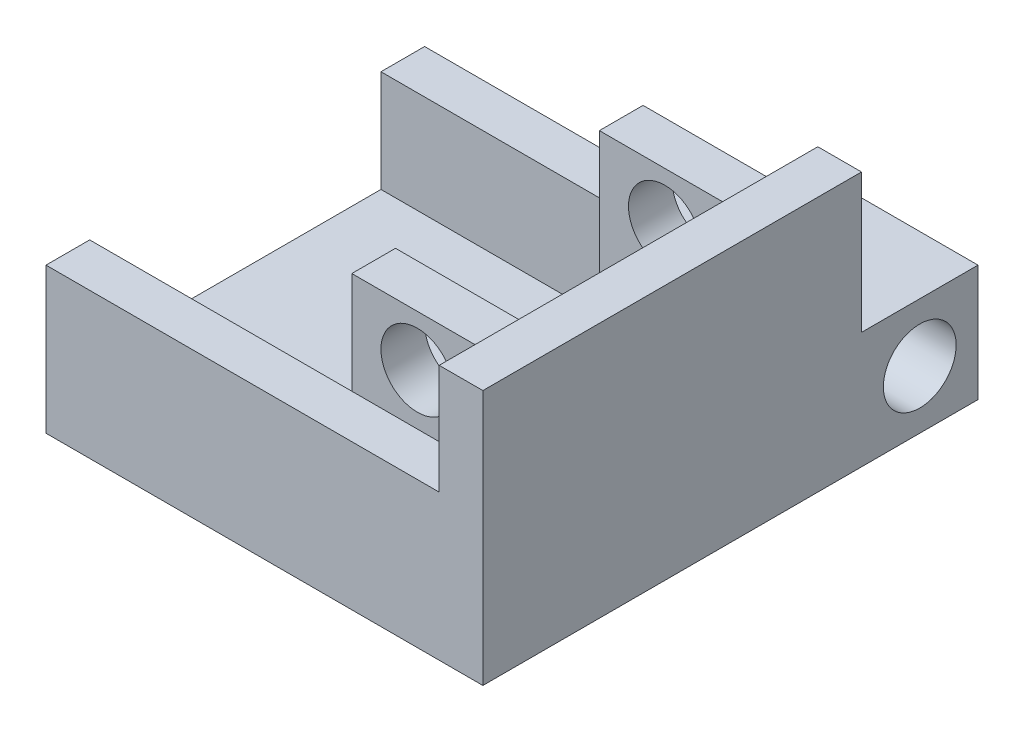
SolidWorks part; units mm, degrees
ref_plane "Front Plane" through (0, 0, 0) normal (0, 0, 1) x (1, 0, 0)
ref_plane "Top Plane" through (0, 0, 0) normal (0, 1, 0) x (1, 0, 0)
ref_plane "Right Plane" through (0, 0, 0) normal (1, 0, 0) x (0, 0, -1)
sketch "Sketch1" plane through (0, 0, 0) normal (0, 1, 0) x (1, 0, 0)
  line L0 (13.5, 10) -> (13.5, 13)
  line L1 (-13.5, -10) -> (13.5, -10)
  line L2 (-13.5, -10) -> (-13.5, 10)
  line L3 (-13.5, 10) -> (13.5, 10)
  line L4 (13.5, -10) -> (13.5, 10)
  line L5 (-13.5, -10) -> (13.5, 10) construction
  line L6 (-13.5, 10) -> (13.5, -10) construction
  line L11 (13.5, 13) -> (4.5, 13)
  line L12 (4.5, 13) -> (4.5, 10)
  line L13 (13.5, -10) -> (13.5, -13)
  line L14 (13.5, -13) -> (4.5, -13)
  line L15 (4.5, -13) -> (4.5, -10)
  line L16 (13.5, 13) -> (16.5, 13)
  line L17 (16.5, 13) -> (16.5, -13)
  line L18 (16.5, -13) -> (13.5, -13)
  line L19 (4.5, -13) -> (-13.5, -13)
  line L20 (-13.5, -13) -> (-13.5, -10)
  line L21 (4.5, 13) -> (-13.5, 13)
  line L22 (-13.5, 13) -> (-13.5, 10)
  point P0 (0, 0)
  point P6 (0, 0)
  dimension "D1" = 27
  dimension "D2" = 20
  dimension "D3" = 3
  dimension "D4" = 9
  dimension "D5" = 3
extrude "Boss-Extrude1" add sketch "Sketch1" along normal blind 3 contours L1 L4 L3 L2 | L11 L12 L3 L0 | L15 L14 L13 L1
extrude "Boss-Extrude2" add sketch "Sketch1<4>" along normal blind 4 from surface contours L15 L14 L13 L1 | L11 L12 L3 L0 region at (9, 0, -11.5) region at (9, 0, 11.5) starting at face at (2.25, 3, 0)
sketch "Sketch1<4>" plane through (0, 0, 0) normal (0, 1, 0) x (1, 0, 0) same geometry as "Sketch1"
sketch "Sketch2" plane through (0, 7, 0) normal (0, 1, 0) x (1, 0, 0)
  line L0 (13.5, -10) -> (13.5, 10) construction
  line L1 (4.5, -13) -> (13.5, -13)
  line L2 (4.5, -13) -> (4.5, -7)
  line L3 (4.5, -7) -> (13.5, -7)
  line L4 (13.5, -13) -> (13.5, -7)
  line L6 (4.5, 13) -> (13.5, 13)
  line L7 (4.5, 13) -> (4.5, 7)
  line L8 (4.5, 7) -> (13.5, 7)
  line L9 (13.5, 13) -> (13.5, 7)
  dimension "D1" = 6
extrude "Boss-Extrude3" add sketch "Sketch2" along normal blind 3
extrude "Boss-Extrude4" add sketch "Sketch2<2>" along normal blind 2 from surface starting at face at (1.5, 3, 0)
sketch "Sketch2<2>" plane through (0, 7, 0) normal (0, 1, 0) x (1, 0, 0) same geometry as "Sketch2"
extrude "Boss-Extrude5" add sketch "Sketch1<5>" along normal up to surface (10 mm away) contours L18 L17 L16 L0 L4 L13 | L20 L19 L15 L1 | L21 L22 L3 L12 region at (15, 0, 0) region at (-4.5, 0, -11.5) region at (-4.5, 0, 11.5) up to face at (9, 10, -10)
sketch "Sketch1<5>" plane through (0, 0, 0) normal (0, 1, 0) x (1, 0, 0) same geometry as "Sketch1"
sketch "Sketch3" plane through (0, 10, 0) normal (0, 1, 0) x (1, 0, 0)
  line L0 (-13.5, -13) -> (16.5, -13) construction
  line L1 (16.5, 13) -> (13.5, 13)
  line L2 (16.5, 13) -> (16.5, -13)
  line L3 (16.5, -13) -> (13.5, -13)
  line L4 (13.5, 13) -> (13.5, -13)
  line L5 (13.5, -7) -> (13.5, 7) construction
extrude "Boss-Extrude6" add sketch "Sketch3" along normal blind 7.54
sketch "Sketch4" plane through (0, 10, 0) normal (0, 1, 0) x (1, 0, 0)
  line L0 (13.5, -7) -> (13.5, -13) construction
  line L1 (4.5, 10) -> (13.5, 10)
  line L2 (4.5, 10) -> (4.5, 7)
  line L3 (4.5, 7) -> (13.5, 7)
  line L4 (13.5, 10) -> (13.5, 7)
  line L5 (4.5, -7) -> (13.5, -7)
  line L6 (4.5, -7) -> (4.5, -10)
  line L7 (4.5, -10) -> (13.5, -10)
  line L8 (13.5, -7) -> (13.5, -10)
extrude "Boss-Extrude7" add sketch "Sketch4" along normal blind 7
sketch "Sketch5" plane through (0, 0, 10) normal (0, 0, 1) x (1, 0, 0)
  line L0 (9, 17) -> (9, 13.5) construction
  line L1 (4.5, 17) -> (13.5, 17) construction
  line L5 (4.5, 17) -> (4.5, 10) construction
  line L6 (13.5, 17.54) -> (13.5, 10) construction
  line L7 (4.5, 13.5) -> (13.5, 13.5) construction
  circle A0 centre (9, 13.5) radius 2.5
  dimension "D1" = 5
extrude "Cut-Extrude1" cut sketch "Sketch5" against normal through all both and the other way through all
sketch "Sketch6" plane through (16.5, 0, 0) normal (1, 0, 0) x (0, 0, -1)
  line L0 (13, 8) -> (21, 0) construction
  line L1 (13, 0) -> (21, 0)
  line L2 (13, 0) -> (13, 8)
  line L3 (13, 8) -> (21, 8)
  line L4 (21, 0) -> (21, 8)
  circle A0 centre (17, 4) radius 2.5
  point P7 (17, 4)
  dimension "D3" = 5
  dimension "D1" = 8
  dimension "D2" = 8
extrude "Boss-Extrude8" add sketch "Sketch6" against normal blind 10
